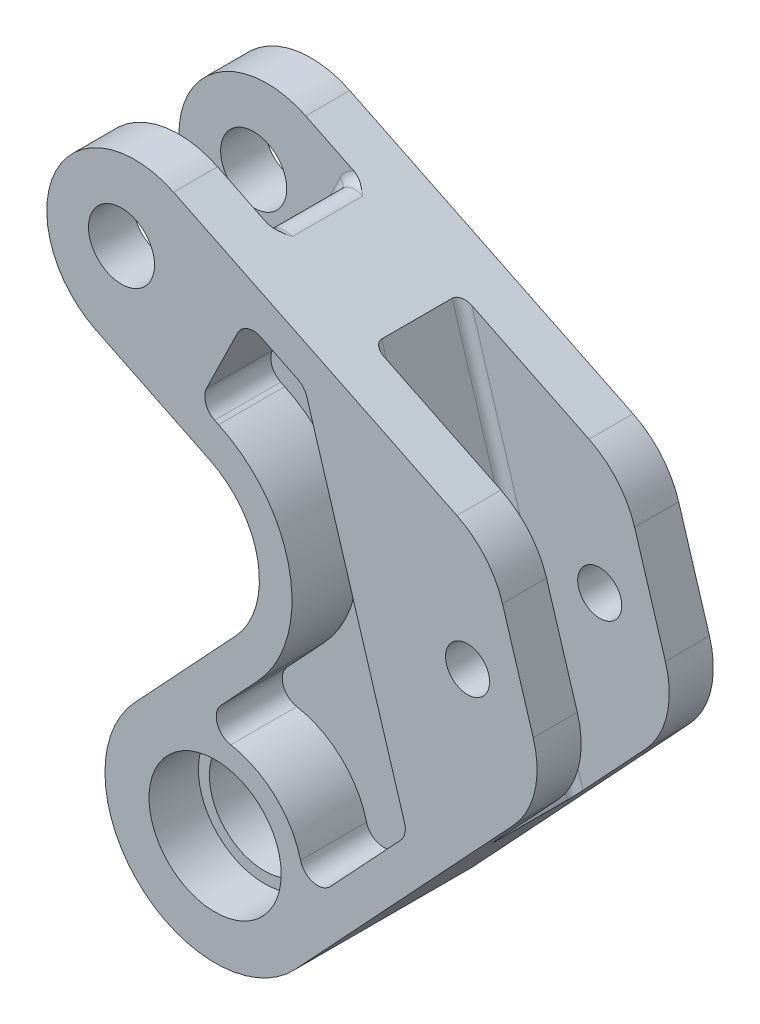
SolidWorks part; units mm, degrees
material "6061-T6 (SS)"
ref_plane "X-Y Datum" through (0, 0, 0) normal (0, 0, 1) x (1, 0, 0)
ref_plane "X-Z Datum" through (0, 0, 0) normal (0, 1, 0) x (1, 0, 0)
ref_plane "Y-Z Datum" through (0, 0, 0) normal (1, 0, 0) x (0, 0, -1)
sketch "Sketch1" plane through (0, 0, 0) normal (0, 0, 1) x (1, 0, 0)
  line L0 (0, 0) -> (36.3909, 38.9981)
  line L1 (31.7483, 64.0948) -> (-19.53, 89.1263)
  line L2 (-30.6723, 66.3007) -> (3.0712, 49.8288)
  line L3 (3.0712, 49.8288) -> (-23.2132, 21.6613)
  arc A0 (36.3909, 38.9981) -> (31.7483, 64.0948) centre (24.7844, 49.8288) ccw
  arc A1 (-19.53, 89.1263) -> (-30.6723, 66.3007) centre (-25.1012, 77.7135) ccw
  arc A2 (-23.2132, 21.6613) -> (0, 0) centre (-11.6066, 10.8306) ccw
  dimension "D1" = 53.34
  dimension "D2" = 73
  dimension "D3" = 57.15
  dimension "D5" = 25.4
  dimension "D7" = 15.875
  dimension "D8" = 12.7
extrude "Boss-Extrude1" add sketch "Sketch1" along normal blind 25.4 contours L3 A2 L0 A0 L1 A1 L2
fillet "Fillet1" radius 12.7 1 edges at (3.0712, 49.8288, 12.7)
sketch "Sketch2" plane through (0, 0, 25.4) normal (0, 0, 1) x (1, 0, 0)
  circle A0 centre (-11.6066, 10.8306) radius 7.9375
  circle A1 centre (24.7844, 49.8288) radius 3.175
  circle A2 centre (-25.1012, 77.7135) radius 4.7625
  point P9 (0, 0)
  point P10 (0, 0)
  dimension "D1" = 6.35
  dimension "D2" = 9.525
  dimension "D3" = 15.875
extrude "Cut-Extrude1" cut sketch "Sketch2" against normal blind 25.4
sketch "Sketch8" plane through (0, 0, 25.4) normal (0, 0, 1) x (1, 0, 0)
  circle A0 centre (-11.6066, 10.8306) radius 9.525
  dimension "D1" = 19.05
extrude "Cut-Extrude4" cut sketch "Sketch8" against normal blind 7.112
ref_plane "Plane3" through (0, 0, 12.7) normal (0, 0, 1) x (1, 0, 0)
mirror "Mirror1" about plane through (0, 0, 12.7) normal (0, 0, 1) of "Cut-Extrude4"
ref_plane "Plane1" through (-7.789, 25.5073, 0) normal (0.292, -0.9564, 0) x (0, 0, -1)
sketch "Sketch3" plane through (-7.789, 25.5073, 0) normal (0.292, -0.9564, 0) x (0, 0, -1)
  line L0 (-19.05, 54.1313) -> (-19.05, 27.1438)
  line L1 (0, 54.1313) -> (-25.4, 54.1313) construction
  line L2 (-19.05, 27.1438) -> (-6.35, 27.1438)
  line L3 (-6.35, 27.1438) -> (-6.35, 54.1313)
  line L4 (-25.4, 0) -> (-25.4, 46.1938) construction
  line L5 (-25.4, 46.1938) -> (0, 46.1938) construction
  dimension "D1" = 12.7
  dimension "D2" = 6.35
  dimension "D3" = 19.05
extrude "Cut-Extrude2" cut sketch "Sketch3" against normal through all and the other way through all
ref_plane "Plane2" through (31.3765, 64.2763, 0) normal (-0.4387, -0.8986, 0) x (-0.8986, 0.4387, 0)
sketch "Sketch7" plane through (31.3765, 64.2763, 0) normal (-0.4387, -0.8986, 0) x (-0.8986, 0.4387, 0)
  line L6 (-0.4138, 0) -> (56.648, 0) construction
  line L7 (46.488, -19.05) -> (69.983, -19.05)
  line L8 (46.488, -19.05) -> (46.488, -6.35)
  line L9 (46.488, -6.35) -> (69.983, -6.35)
  line L10 (69.983, -19.05) -> (69.983, -6.35)
  line L11 (56.648, -25.4) -> (56.648, 0) construction
  dimension "D1" = 12.7
  dimension "D2" = 6.35
  dimension "D3" = 23.495
  dimension "D4" = 10.16
extrude "Cut-Extrude3" cut sketch "Sketch7" against normal mid plane 53.34
fillet "Fillet2" radius 2.54 2 edges at (-21.5421, 61.8438, 12.7) (-10.3998, 84.6694, 12.7)
fillet "Fillet3" radius 1.27 8 edges at (13.0871, 50.0849, 19.05) (13.0871, 50.0849, 6.35) (-15.9709, 73.2566, 19.05) (-10.0576, 83.6745, 19.05) (-20.5472, 62.1859, 19.05) (-10.0576, 83.6745, 6.35) (-20.5472, 62.1859, 6.35) (-15.9709, 73.2566, 6.35)
sketch3d "3DSketch1"
  line L0 (24.7844, 49.8288, 0) -> (24.7844, 49.8288, 25.4) construction
  line L1 (24.7844, 49.8288, 0) -> (24.7844, 49.8288, 6.35) construction
  line L2 (24.7844, 49.8288, 19.05) -> (24.7844, 49.8288, 25.4) construction
  line L3 (24.7844, 49.8288, 25.4) -> (24.7844, 49.8288, 19.05) construction
  point P8 (24.7844, 49.8288, 12.7)
sketch3d "3DSketch2"
  line L0 (-25.1012, 77.7135, 0) -> (-25.1012, 77.7135, 25.4) construction
  line L1 (-25.1012, 77.7135, 0) -> (-25.1012, 77.7135, 6.35) construction
  line L2 (-25.1012, 77.7135, 19.05) -> (-25.1012, 77.7135, 25.4) construction
  point P6 (-25.1012, 77.7135, 12.7)
sketch "Sketch9" plane through (0, 0, 25.4) normal (0, 0, 1) x (1, 0, 0)
  line L0 (0.8502, 8.3571) -> (16.1244, 24.7256)
  line L1 (16.1244, 24.7256) -> (1.2883, 73.3109)
  line L2 (1.2883, 73.3109) -> (-7.2713, 77.4893)
  line L3 (-7.2713, 77.4893) -> (-13.9567, 63.7939)
  line L4 (-13.9567, 63.7939) -> (-11.1035, 62.4011)
  line L5 (-5.4607, 33.2397) -> (-14.9348, 23.0868)
  line L6 (0, 0) -> (36.3909, 38.9981) construction
  line L7 (28.1982, 65.8278) -> (36.3909, 38.9981)
  line L8 (31.7483, 64.0948) -> (-19.53, 89.1263) construction
  line L9 (-30.6723, 66.3007) -> (-12.3523, 57.3578) construction
  line L10 (-8.6382, 37.2805) -> (-23.2132, 21.6613) construction
  line L11 (36.3909, 38.9981) -> (44.4539, 41.4603)
  line L12 (44.4539, 41.4603) -> (36.2612, 68.2899)
  line L13 (36.2612, 68.2899) -> (28.1982, 65.8278)
  line L15 (-31.4787, 88.6961) -> (-37.6831, 75.986)
  line L16 (-31.4787, 88.6961) -> (-34.5809, 90.2104)
  line L17 (-34.5809, 90.2104) -> (-40.7907, 77.4893)
  line L18 (-40.7907, 77.4893) -> (-37.6831, 75.986)
  arc A0 (0.8502, 8.3571) -> (-14.9348, 23.0868) centre (-11.6066, 10.8306) ccw
  arc A1 (-11.1035, 62.4011) -> (-5.4607, 33.2397) centre (-18.8869, 45.7683) cw
  arc A2 (-19.53, 89.1263) -> (-30.6723, 66.3007) centre (-25.1012, 77.7135) ccw construction
  dimension "D1" = 12.7
  dimension "D9" = 18.3639
  dimension "D2" = 5.08
  dimension "D3" = 120
  dimension "D4" = 5.08
  dimension "D5" = 50.8
  dimension "D6" = 5.08
  dimension "D7" = 9.525
  dimension "D8" = 5.08
  dimension "D10" = 3.175
  dimension "D11" = 26.67
extrude "Cut-Extrude5" cut sketch "Sketch9" against normal blind 9.525
mirror "Mirror2" about plane through (0, 0, 12.7) normal (0, 0, 1) of "Cut-Extrude5"
fillet "Fillet4" radius 2.54 12 edges at (-13.9567, 63.7939, 4.7625) (-14.9348, 23.0868, 4.7625) (0.8502, 8.3571, 4.7625) (16.1244, 24.7256, 4.7625) (1.2883, 73.3109, 4.7625) (-7.2713, 77.4893, 4.7625) (-13.9567, 63.7939, 20.6375) (-7.2713, 77.4893, 20.6375) (1.2883, 73.3109, 20.6375) (16.1244, 24.7256, 20.6375) (0.8502, 8.3571, 20.6375) (-14.9348, 23.0868, 20.6375)
fillet "Fillet5" radius 12.7 8 edges at (36.3909, 38.9981, 3.175) (36.3909, 38.9981, 22.225) (28.1982, 65.8278, 3.175) (28.1982, 65.8278, 22.225) (-37.6831, 75.986, 22.225) (-31.4787, 88.6961, 22.225) (-37.6831, 75.986, 3.175) (-31.4787, 88.6961, 3.175)
